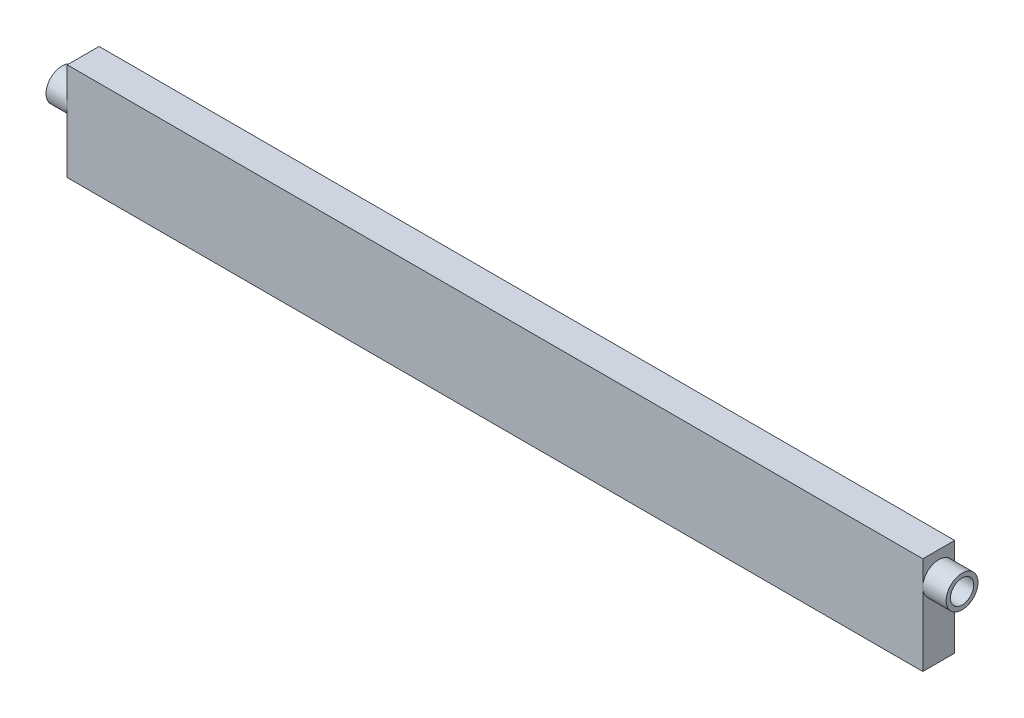
SolidWorks part; units mm, degrees
ref_plane "Płaszczyzna przednia" through (0, 0, 0) normal (0, 0, 1) x (1, 0, 0)
ref_plane "Płaszczyzna górna" through (0, 0, 0) normal (0, 1, 0) x (1, 0, 0)
ref_plane "Płaszczyzna prawa" through (0, 0, 0) normal (1, 0, 0) x (0, 0, -1)
sketch "Szkic1" plane through (0, 0, 0) normal (0, 0, 1) x (1, 0, 0)
  line L0 (0, 33) -> (26.7925, 44.0978)
  line L1 (0, 0) -> (403, 0)
  line L2 (0, 0) -> (0, 46)
  line L3 (0, 46) -> (403, 46)
  line L4 (403, 0) -> (403, 46)
  line L5 (34.3588, 20.2989) -> (91.8145, 44.0978)
  line L6 (0, 25.4233) -> (1.8478, 26.1886)
  line L7 (1.8478, 26.1886) -> (59.3035, 2.3897)
  line L8 (10.9937, 29.977) -> (29.4713, 37.6307)
  line L9 (10.9937, 29.977) -> (24.0593, 24.565)
  line L10 (24.0593, 24.565) -> (33.2981, 28.3919)
  line L11 (32.511, 21.0642) -> (34.3588, 20.2989)
  line L12 (65.022, 25.4233) -> (66.8698, 26.1886)
  line L13 (43.5047, 16.5105) -> (61.9823, 8.8568)
  line L14 (43.5047, 16.5105) -> (56.5703, 21.9225)
  line L15 (56.5703, 21.9225) -> (65.8091, 18.0956)
  line L16 (76.0157, 29.977) -> (94.4933, 37.6307)
  line L17 (89.0813, 24.565) -> (98.3201, 28.3919)
  line L18 (76.0157, 29.977) -> (89.0813, 24.565)
  line L19 (66.8698, 26.1886) -> (124.3255, 2.3897)
  line L20 (99.3808, 20.2989) -> (156.8365, 44.0978)
  line L21 (121.5923, 21.9225) -> (130.8311, 18.0956)
  line L22 (97.533, 21.0642) -> (99.3808, 20.2989)
  line L23 (108.5267, 16.5105) -> (121.5923, 21.9225)
  line L24 (108.5267, 16.5105) -> (127.0043, 8.8568)
  line L25 (130.044, 25.4233) -> (131.8918, 26.1886)
  line L26 (141.0377, 29.977) -> (159.5153, 37.6307)
  line L27 (154.1033, 24.565) -> (163.3421, 28.3919)
  line L28 (141.0377, 29.977) -> (154.1033, 24.565)
  line L29 (131.8918, 26.1886) -> (189.3475, 2.3897)
  line L30 (164.4027, 20.2989) -> (221.8585, 44.0978)
  line L31 (186.6143, 21.9225) -> (195.8531, 18.0956)
  line L32 (162.555, 21.0642) -> (164.4027, 20.2989)
  line L33 (173.5487, 16.5105) -> (186.6143, 21.9225)
  line L34 (173.5487, 16.5105) -> (192.0263, 8.8568)
  line L35 (195.066, 25.4233) -> (196.9137, 26.1886)
  line L36 (206.0597, 29.977) -> (224.5373, 37.6307)
  line L37 (219.1253, 24.565) -> (228.3641, 28.3919)
  line L38 (206.0597, 29.977) -> (219.1253, 24.565)
  line L39 (196.9137, 26.1886) -> (254.3695, 2.3897)
  line L40 (229.4247, 20.2989) -> (286.8805, 44.0978)
  line L41 (251.6363, 21.9225) -> (260.8751, 18.0956)
  line L42 (227.577, 21.0642) -> (229.4247, 20.2989)
  line L43 (238.5707, 16.5105) -> (251.6363, 21.9225)
  line L44 (238.5707, 16.5105) -> (257.0483, 8.8568)
  line L45 (260.088, 25.4233) -> (261.9357, 26.1886)
  line L46 (271.0817, 29.977) -> (289.5593, 37.6307)
  line L47 (284.1473, 24.565) -> (293.3861, 28.3919)
  line L48 (271.0817, 29.977) -> (284.1473, 24.565)
  line L49 (261.9357, 26.1886) -> (319.3915, 2.3897)
  line L50 (294.4467, 20.2989) -> (351.9025, 44.0978)
  line L51 (316.6583, 21.9225) -> (325.8971, 18.0956)
  line L52 (292.599, 21.0642) -> (294.4467, 20.2989)
  line L53 (303.5927, 16.5105) -> (316.6583, 21.9225)
  line L54 (303.5927, 16.5105) -> (322.0703, 8.8568)
  line L55 (325.11, 25.4233) -> (326.9577, 26.1886)
  line L56 (336.1037, 29.977) -> (354.5813, 37.6307)
  line L57 (349.1693, 24.565) -> (358.4081, 28.3919)
  line L58 (336.1037, 29.977) -> (349.1693, 24.565)
  line L59 (326.9577, 26.1886) -> (384.4135, 2.3897)
  line L60 (359.4687, 20.2989) -> (416.9245, 44.0978)
  line L61 (381.6803, 21.9225) -> (390.9191, 18.0956)
  line L62 (357.621, 21.0642) -> (359.4687, 20.2989)
  line L63 (368.6147, 16.5105) -> (381.6803, 21.9225)
  line L64 (368.6147, 16.5105) -> (387.0923, 8.8568)
  line L65 (390.132, 25.4233) -> (391.9797, 26.1886)
  line L66 (391.9797, 26.1886) -> (403, 30.7534)
  line L67 (10.9937, 29.977) -> (8.3149, 23.5098) construction
  line L68 (23.3282, 35.0861) -> (20.6494, 41.5533) construction
  line L69 (57.6712, 10.6426) -> (54.9924, 4.1754) construction
  line L70 (50.0375, 19.2165) -> (47.3587, 25.6836) construction
  arc A0 (26.7925, 44.0978) -> (32.511, 21.0642) centre (31.3847, 33.0113) cw
  arc A1 (29.4713, 37.6307) -> (33.2981, 28.3919) centre (31.3847, 33.0113) cw
  arc A2 (59.3035, 2.3897) -> (65.022, 25.4233) centre (63.8957, 13.4762) ccw
  arc A3 (65.8091, 18.0956) -> (61.9823, 8.8568) centre (63.8957, 13.4762) cw
  arc A4 (91.8145, 44.0978) -> (97.533, 21.0642) centre (96.4067, 33.0113) cw
  arc A5 (94.4933, 37.6307) -> (98.3201, 28.3919) centre (96.4067, 33.0113) cw
  arc A6 (124.3255, 2.3897) -> (130.044, 25.4233) centre (128.9177, 13.4762) ccw
  arc A7 (130.8311, 18.0956) -> (127.0043, 8.8568) centre (128.9177, 13.4762) cw
  arc A8 (156.8365, 44.0978) -> (162.555, 21.0642) centre (161.4287, 33.0113) cw
  arc A9 (159.5153, 37.6307) -> (163.3421, 28.3919) centre (161.4287, 33.0113) cw
  arc A10 (189.3475, 2.3897) -> (195.066, 25.4233) centre (193.9397, 13.4762) ccw
  arc A11 (195.8531, 18.0956) -> (192.0263, 8.8568) centre (193.9397, 13.4762) cw
  arc A12 (221.8585, 44.0978) -> (227.577, 21.0642) centre (226.4507, 33.0113) cw
  arc A13 (224.5373, 37.6307) -> (228.3641, 28.3919) centre (226.4507, 33.0113) cw
  arc A14 (254.3695, 2.3897) -> (260.088, 25.4233) centre (258.9617, 13.4762) ccw
  arc A15 (260.8751, 18.0956) -> (257.0483, 8.8568) centre (258.9617, 13.4762) cw
  arc A16 (286.8805, 44.0978) -> (292.599, 21.0642) centre (291.4727, 33.0113) cw
  arc A17 (289.5593, 37.6307) -> (293.3861, 28.3919) centre (291.4727, 33.0113) cw
  arc A18 (319.3915, 2.3897) -> (325.11, 25.4233) centre (323.9837, 13.4762) ccw
  arc A19 (325.8971, 18.0956) -> (322.0703, 8.8568) centre (323.9837, 13.4762) cw
  arc A20 (351.9025, 44.0978) -> (357.621, 21.0642) centre (356.4947, 33.0113) cw
  arc A21 (354.5813, 37.6307) -> (358.4081, 28.3919) centre (356.4947, 33.0113) cw
  arc A22 (384.4135, 2.3897) -> (390.132, 25.4233) centre (389.0057, 13.4762) ccw
  arc A23 (390.9191, 18.0956) -> (387.0923, 8.8568) centre (389.0057, 13.4762) cw
  dimension "D6" = 5
  dimension "D1" = 7
  dimension "D3" = 10
  dimension "D4" = 135
  dimension "D5" = 2
  dimension "D8" = 67.5
  dimension "D9" = 13
  dimension "D10" = 46
  dimension "D12" = 2
  dimension "D14" = 403
  dimension "D13" = 6
extrude "Dodanie-wyciągnięcie1" add sketch "Szkic1" along normal blind 12 contours A22 L59 L55 A18 L49 L45 A14 L39 L35 A10 L29 L25 A6 L19 L12 A2 L7 L6 L2 L1 L4 L66 L65 | A1 L8 L9 L10 | A3 L15 L14 L13 | A5 L16 L18 L17 | A7 L21 L23 L24 | A9 L26 L28 L27 | A11 L31 L33 L34 | A13 L36 L38 L37 | A15 L41 L43 L44 | A17 L46 L48 L47 | A19 L51 L53 L54 | A21 L56 L58 L57 | A23 L61 L63 L64 | L50 A20 L62 L60 L4 L3 L2 L0 A0 L11 L5 A4 L22 L20 A8 L32 L30 A12 L42 L40 A16 L52 region at (207.4297, 38.6025, 0) region at (2.4706, 22.0719, 0) region at (25.9282, 31.2277, 0) region at (58.4392, 15.2598, 0) region at (90.9502, 31.2277, 0) region at (123.4612, 15.2598, 0) region at (155.9722, 31.2277, 0) region at (188.4832, 15.2598, 0) region at (220.9941, 31.2277, 0) region at (253.5051, 15.2598, 0) region at (286.0161, 31.2277, 0) region at (318.5271, 15.2598, 0) region at (351.0381, 31.2277, 0) region at (383.5491, 15.2598, 0)
extrude "Dodanie-wyciągnięcie2" add sketch "Szkic1<3>" against normal blind 1.5 contours L1 L4 L3 L2
sketch "Szkic1<3>" plane through (0, 0, 0) normal (0, 0, 1) x (1, 0, 0) same geometry as "Szkic1"
extrude "Dodanie-wyciągnięcie3" add sketch "Szkic1<4>" along normal blind 1.5 from offset 12 contours L1 L4 L3 L2
sketch "Szkic1<4>" plane through (0, 0, 0) normal (0, 0, 1) x (1, 0, 0) same geometry as "Szkic1"
sketch "Szkic2" plane through (0, 0, 0) normal (-1, 0, 0) x (0, 0, 1)
  line L0 (13.5, 0) -> (13.5, 46) construction
  line L1 (-1.5, 0) -> (-1.5, 46) construction
  line L3 (-1.5, 46) -> (13.5, 46) construction
  circle A0 centre (6, 29.25) radius 7.5
  point P7 (6, 29.2593)
  point P13 (0, 0)
  line M4 (12, 33) -> (12, 25.4233)
  line M5 (12, 25.4233) -> (0, 25.4233)
  line M6 (0, 25.4233) -> (0, 33)
  line M7 (0, 33) -> (12, 33)
  dimension "D1" = 16.75
extrude "Dodanie-wyciągnięcie6" add sketch "Szkic2" along normal blind 10 and the other way blind 2 contours A0 M7 M4 M5 M6 | M4 M7 M6 M5 region at (0, 29.25, -1.2879) region at (0, 29.2116, 6)
sketch "Szkic3" plane through (-10, 0, 0) normal (-1, 0, 0) x (0, 0, 1)
  circle A0 centre (6, 29.25) radius 5.5
  dimension "D1" = 11
extrude "Wytnij-wyciągnięcie1" cut sketch "Szkic3" against normal blind 18
sketch "Szkic4" plane through (403, 0, 0) normal (1, 0, 0) x (0, 0, -1)
  line L0 (1.5, 0) -> (1.5, 46) construction
  line L1 (-13.5, 0) -> (-13.5, 46) construction
  line L2 (1.5, 46) -> (-13.5, 46) construction
  circle A0 centre (-6, 34.4) radius 7.5
  circle A1 centre (-6, 34.4) radius 5.5
  dimension "D2" = 11
  dimension "D1" = 11.6
extrude "Dodanie-wyciągnięcie8" add sketch "Szkic4" along normal blind 11 and the other way blind 2
extrude "Wytnij-wyciągnięcie2" cut sketch "Szkic4<2>" against normal blind 9 contours A1
sketch "Szkic4<2>" plane through (403, 0, 0) normal (1, 0, 0) x (0, 0, -1) same geometry as "Szkic4"
